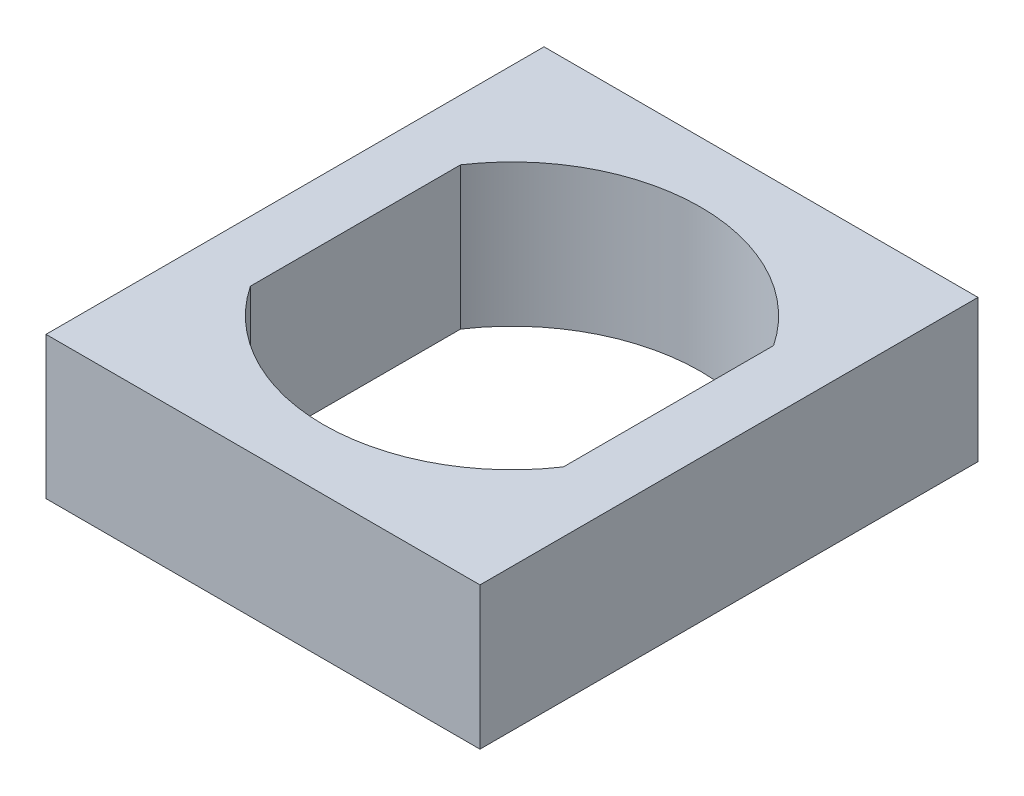
SolidWorks part; units mm, degrees
ref_plane "Front Plane" through (0, 0, 0) normal (0, 0, 1) x (1, 0, 0)
ref_plane "Top Plane" through (0, 0, 0) normal (0, 1, 0) x (1, 0, 0)
ref_plane "Right Plane" through (0, 0, 0) normal (1, 0, 0) x (0, 0, -1)
sketch "Sketch1" plane through (0, 45.5089, 0) normal (0, 1, 0) x (1, 0, 0)
  line L0 (28.9803, -65.4258) -> (32.2528, -65.4258) construction
  line L1 (27.3666, -72.8258) -> (33.8666, -72.8258) construction
  line L2 (27.3666, -72.8258) -> (27.3666, -65.4258) construction
  line L3 (27.3666, -65.4258) -> (33.8666, -65.4258) construction
  line L4 (33.8666, -72.8258) -> (33.8666, -65.4258) construction
  line L5 (28.9803, -72.8258) -> (32.2528, -72.8258) construction
  line L6 (27.3666, -71.5517) -> (27.3666, -66.7) construction
  line L7 (33.8666, -71.5517) -> (33.8666, -66.7) construction
  line L8 (27.5666, -72.6258) -> (33.6666, -72.6258)
  line L9 (33.6666, -72.6258) -> (33.6666, -65.6258)
  line L10 (27.5666, -65.6258) -> (33.6666, -65.6258)
  line L11 (27.5666, -72.6258) -> (27.5666, -65.6258)
  line L12 (28.5166, -67.6793) -> (28.5166, -70.5724) construction
  line L13 (32.7166, -67.6793) -> (32.7166, -70.5724) construction
  line L14 (28.5166, -69.1258) -> (30.6166, -69.1258) construction
  line L15 (30.6166, -69.1258) -> (32.7166, -69.1258) construction
  line L16 (32.8166, -67.6485) -> (32.8166, -70.6032)
  line L17 (28.4166, -67.6485) -> (28.4166, -70.6032)
  arc A0 (32.7166, -67.6793) -> (28.5166, -67.6793) centre (30.6166, -69.1258) ccw construction
  arc A1 (28.5166, -70.5724) -> (32.7166, -70.5724) centre (30.6166, -69.1258) ccw construction
  arc A2 (28.4166, -70.6032) -> (32.8166, -70.6032) centre (30.6166, -69.1258) ccw
  arc A3 (32.8166, -67.6485) -> (28.4166, -67.6485) centre (30.6166, -69.1258) ccw
  point P19 (27.5666, -69.1258)
  point P20 (30.6166, -65.6258)
  dimension "D2" = 5.1
  dimension "D3" = 4.2
  dimension "D4" = 0.1
  dimension "D1" = 0.2
extrude "Boss-Extrude1" add sketch "Sketch1" along normal up to surface (2 mm away)
